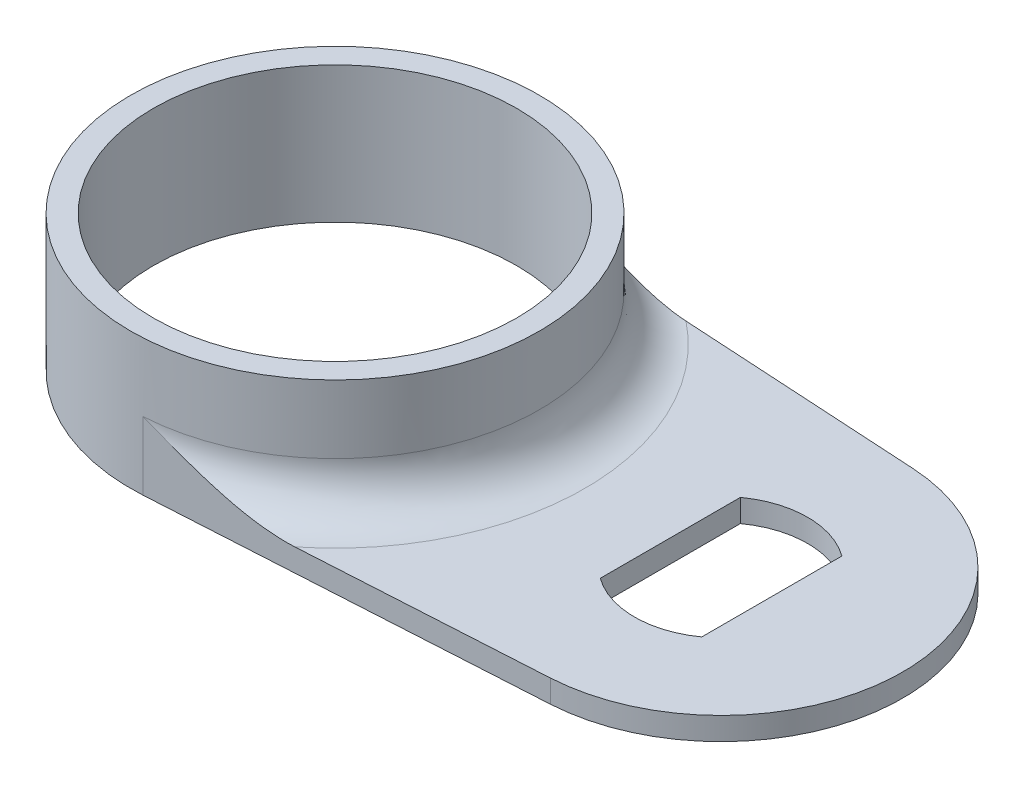
SolidWorks part; units mm, degrees
ref_plane "Front Plane" through (0, 0, 0) normal (0, 0, 1) x (1, 0, 0)
ref_plane "Top Plane" through (0, 0, 0) normal (0, 1, 0) x (1, 0, 0)
ref_plane "Right Plane" through (0, 0, 0) normal (1, 0, 0) x (0, 0, -1)
sketch "Sketch2" plane through (0, 0, 0) normal (0, 1, 0) x (1, 0, 0)
  line L0 (-11.1791, 15.425) -> (-11.1791, -15.425)
  line L1 (11.1791, -15.425) -> (11.1791, 15.425)
  line L2 (-82.3529, 44.9221) -> (2.3529, 39.9307)
  line L3 (-82.3529, -44.9221) -> (2.3529, -39.9307)
  arc A0 (-11.1791, -15.425) -> (11.1791, -15.425) centre (0, 0) ccw
  arc A1 (11.1791, 15.425) -> (-11.1791, 15.425) centre (0, 0) ccw
  arc A2 (2.3529, -39.9307) -> (2.3529, 39.9307) centre (0, 0) ccw
  circle A3 centre (-85, 0) radius 40
  arc A4 (-82.3529, 44.9221) -> (-82.3529, -44.9221) centre (-85, 0) ccw
  dimension "D1" = 38.1
  dimension "D3" = 80
  dimension "D4" = 80
  dimension "D5" = 5
  dimension "D2" = 30.85
extrude "Mount plate" add sketch "Sketch2" along normal blind 5
sketch "Sketch3" plane through (0, 5, 0) normal (0, 1, 0) x (1, 0, 0)
  circle A0 centre (-85, 0) radius 40 construction
  circle A1 centre (-85, 0) radius 40
  circle A2 centre (-85, 0) radius 45
  arc A3 (-82.3529, 44.9221) -> (-82.3529, -44.9221) centre (-85, 0) ccw construction
extrude "Cylinder guide" add sketch "Sketch3" along normal blind 25
fillet "Structural fillet" radius 10 1 edges at (-40, 5, 0)
